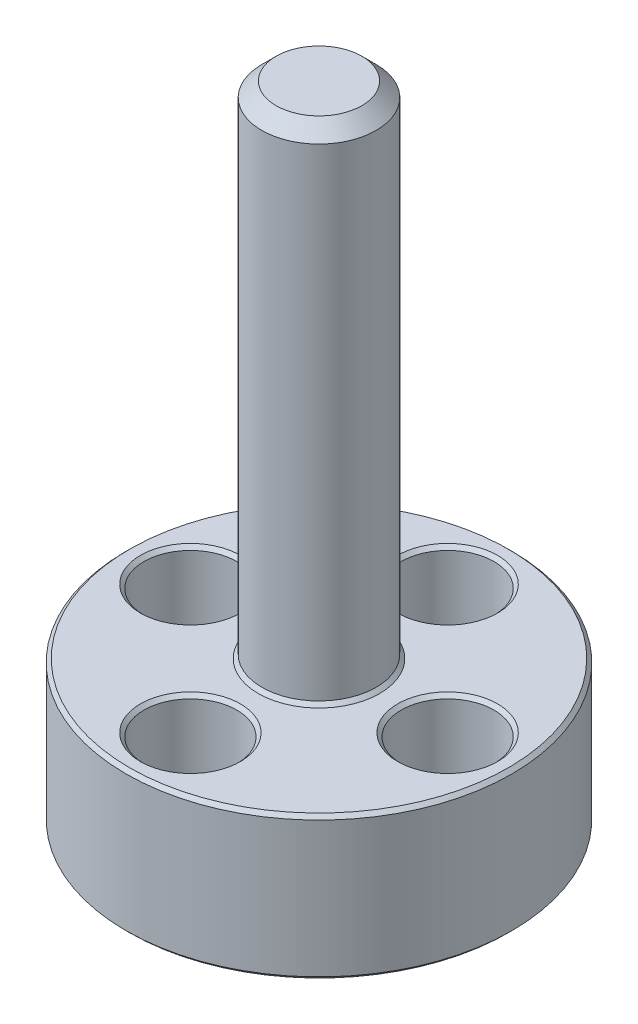
SolidWorks part; units mm, degrees
material "6061 Alloy"
ref_plane "Front Plane" through (0, 0, 0) normal (0, 0, 1) x (1, 0, 0)
ref_plane "Top Plane" through (0, 0, 0) normal (0, 1, 0) x (1, 0, 0)
ref_plane "Right Plane" through (0, 0, 0) normal (1, 0, 0) x (0, 0, -1)
sketch "Sketch2" plane through (0, 0, 0) normal (0, 1, 0) x (1, 0, 0)
  circle A0 centre (0, 0) radius 13.5
  dimension "D1" = 27
extrude "Boss-Extrude1" add sketch "Sketch2" along normal blind 10
sketch "Sketch3" plane through (0, 0, 0) normal (0, 1, 0) x (1, 0, 0)
  circle A0 centre (0, 0) radius 4
  dimension "D1" = 8
extrude "Boss-Extrude2" add sketch "Sketch3" along normal blind 45
cosmetic thread "Cosmetic Thread1" parameters "D1"=30, "D2"=6.619
sketch "Sketch9" plane through (0, 10, 0) normal (0, 1, 0) x (1, 0, 0)
  line L0 (0, 0) -> (-9, 0) construction
  line L2 (0, 0) -> (9, 0) construction
  line L3 (0, 0) -> (0, 9) construction
  line L5 (0, 0) -> (0, -9) construction
  circle A0 centre (0, 0) radius 9 construction
  point P0 (-9, 0)
  point P13 (9, 0)
  point P18 (0, 9)
  point P23 (0, -9)
  point P29 (0, 9)
  point P31 (9, 0)
  point P35 (0, -9)
  dimension "D1" = 18
hole_wizard "CBORE for M3 SHCS1" positions "Sketch9" profile "Sketch8" counterbore size "M3" standard "ANSI Metric" end condition through all
sketch "Sketch8" plane through (-9, 10, 0) normal (1, 0, 0) x (0, 0, 1)
  line L0 (0, 0) -> (0, 10)
  line L1 (0, 10) -> (1.6, 10)
  line L3 (1.6, 10) -> (1.6, 5)
  line L4 (1.6, 5) -> (3.25, 5)
  line L5 (3.25, 5) -> (3.25, 0)
  line L7 (3.25, 0) -> (0, 0)
  line L11 (0, -6.35) -> (0, 107.95) construction
  dimension "Thru Hole Dia." = 3.2
  dimension "Thru Hole Depth" = 10
  dimension "C'Bore Dia." = 6.5
  dimension "C'Bore Depth" = 5
sketch "Sketch10" plane through (0, 0, 0) normal (0, 1, 0) x (1, 0, 0)
  circle A0 centre (0, 0) radius 2.25
  dimension "D1" = 4.5
extrude "Cut-Extrude3" cut sketch "Sketch10" along normal blind 7
chamfer "Chamfer1" distance 0.25 angle 45 12 edges at (0, 0, 13.5) (0, 0, 10.6) (9, 0, 1.6) (0, 0, -7.4) (-9, 0, 1.6) (0, 0, 2.25) (0, 10, 13.5) (0, 10, 4) (0, 10, 12.25) (9, 10, 3.25) (0, 10, -5.75) (-9, 10, 3.25)
chamfer "Chamfer2" distance 1 angle 45 1 edges at (0, 45, 4)
